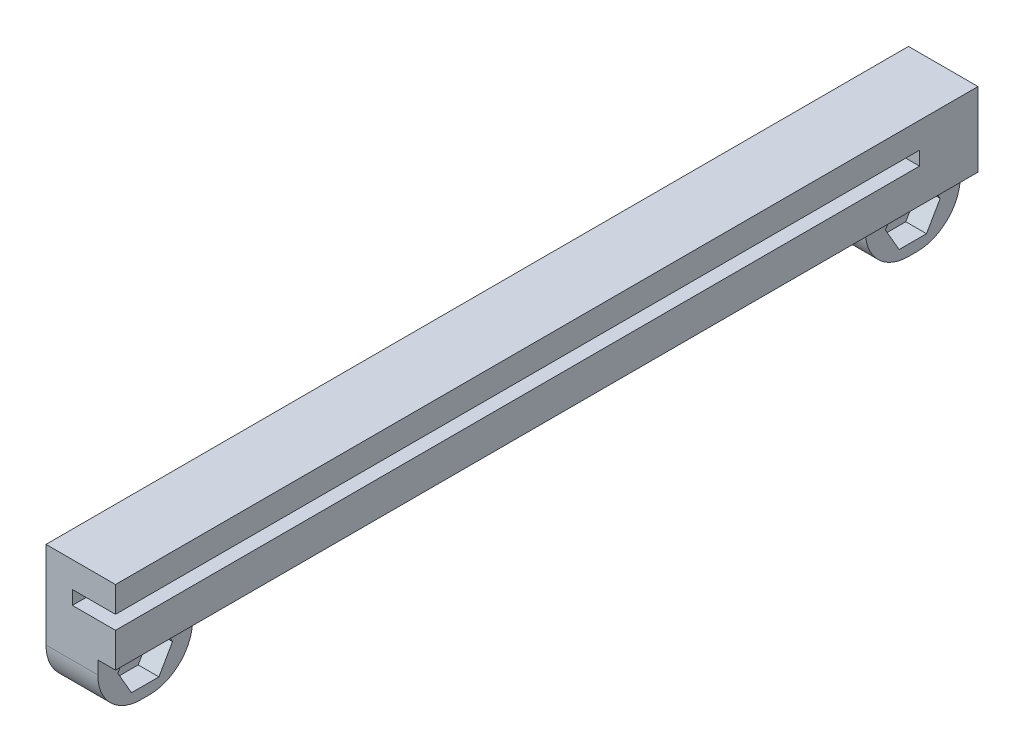
SolidWorks part; units mm, degrees
ref_plane "Front Plane" through (0, 0, 0) normal (0, 0, 1) x (1, 0, 0)
ref_plane "Top Plane" through (0, 0, 0) normal (0, 1, 0) x (1, 0, 0)
ref_plane "Right Plane" through (0, 0, 0) normal (1, 0, 0) x (0, 0, -1)
sketch "Sketch1" plane through (0, 0, 0) normal (0, 1, 0) x (1, 0, 0)
  line L1 (-3.5288, -50) -> (3.5288, -50)
  line L2 (-3.5288, -50) -> (-3.5288, 50)
  line L3 (-3.5288, 50) -> (3.5288, 50)
  line L4 (3.5288, -50) -> (3.5288, 50)
  line L5 (-3.5288, -50) -> (3.5288, 50) construction
  line L6 (-3.5288, 50) -> (3.5288, -50) construction
  point P0 (0, 0)
  dimension "D1" = 100
  dimension "D2" = 7.0575
extrude "Boss-Extrude2" add sketch "Sketch1" along normal blind 7.6
sketch "Sketch4" plane through (0, 7.6, 0) normal (0, 1, 0) x (1, 0, 0)
  line L0 (3.5288, -50) -> (3.5288, 50) construction
  line L1 (3.5288, 43.218) -> (-1.4713, 43.218)
  line L2 (3.5288, 43.218) -> (3.5288, -50)
  line L3 (3.5288, -50) -> (-1.4713, -50)
  line L4 (-1.4713, 43.218) -> (-1.4713, -50)
  line L6 (3.5288, 50) -> (-3.5288, 50) construction
  line L7 (-3.5288, 50) -> (-3.5288, -50) construction
  dimension "D1" = 6.782
  dimension "D2" = 2.0575
extrude "Cut-Extrude1" cut sketch "Sketch4" against normal blind 4.6
sketch "Sketch6" plane through (0, 7.6, 0) normal (0, 1, 0) x (1, 0, 0)
  line L1 (3.5288, 43.218) -> (-1.4713, 43.218)
  line L2 (3.5288, 43.218) -> (3.5288, -50)
  line L3 (3.5288, -50) -> (-1.4713, -50)
  line L4 (-1.4713, 43.218) -> (-1.4713, -50)
extrude "Boss-Extrude3" add sketch "Sketch6" against normal blind 3
sketch "Sketch8" plane through (0, 0, 0) normal (0, -1, 0) x (1, 0, 0)
  line L1 (-3.5288, 50) -> (3.5288, 50)
  line L2 (-3.5288, 50) -> (-3.5288, -50)
  line L3 (-3.5288, -50) -> (3.5288, -50)
  line L4 (3.5288, 50) -> (3.5288, -50)
extrude "Boss-Extrude4" add sketch "Sketch8" along normal blind 1
sketch "Sketch9" plane through (0, -1, 0) normal (0, -1, 0) x (1, 0, 0)
  line L1 (-3.5288, 50) -> (1.4712, 50)
  line L2 (-3.5288, 50) -> (-3.5288, 39)
  line L3 (-3.5288, 39) -> (1.4712, 39)
  line L4 (1.4712, 50) -> (1.4712, 39)
  line L5 (-3.5288, -50) -> (1.4712, -50)
  line L6 (-3.5288, -50) -> (-3.5288, -39)
  line L7 (-3.5288, -39) -> (1.4712, -39)
  line L8 (1.4712, -50) -> (1.4712, -39)
  point P10 (1.4712, -44.5)
  dimension "D1" = 11
  dimension "D2" = 11
  dimension "D3" = 5
  dimension "D4" = 5
extrude "Boss-Extrude5" add sketch "Sketch9" along normal blind 6.5 contours L2 L1 L4 L3 | L6 L5 L8 L7
sketch "Sketch10" plane through (1.4713, 0, 0) normal (1, 0, 0) x (0, 0, -1)
  line L0 (-50, -7.5) -> (-50, -1) construction
  line L1 (-46.0877, -0.75) -> (-47.6754, -3.5)
  line L2 (-47.6754, -3.5) -> (-46.0877, -6.25)
  line L3 (-46.0877, -6.25) -> (-42.9123, -6.25)
  line L4 (-42.9123, -6.25) -> (-41.3246, -3.5)
  line L5 (-41.3246, -3.5) -> (-42.9123, -0.75)
  line L6 (-42.9123, -0.75) -> (-46.0877, -0.75)
  line L7 (-50, -7.5) -> (-39, -7.5) construction
  line L8 (39, -7.5) -> (39, -1) construction
  line L9 (47.6754, -3.5) -> (46.0877, -0.75)
  line L10 (46.0877, -0.75) -> (42.9123, -0.75)
  line L11 (42.9123, -0.75) -> (41.3246, -3.5)
  line L12 (41.3246, -3.5) -> (42.9123, -6.25)
  line L13 (42.9123, -6.25) -> (46.0877, -6.25)
  line L14 (46.0877, -6.25) -> (47.6754, -3.5)
  line L15 (50, -7.5) -> (39, -7.5) construction
  circle A0 centre (-44.5, -3.5) radius 2.75 construction
  circle A1 centre (44.5, -3.5) radius 2.75 construction
  dimension "D1" = 5.5
  dimension "D2" = 5.5
  dimension "D3" = 1.25
  dimension "D4" = 5.5
  dimension "D5" = 1.25
  dimension "D6" = 5.5
extrude "Cut-Extrude2" cut sketch "Sketch10" against normal blind 2.4
sketch "Sketch11" plane through (-0.9287, 0, 0) normal (1, 0, 0) x (0, 0, -1)
  line L2 (-50, -7.5) -> (-39, -7.5) construction
  line L3 (-50, -7.5) -> (-50, -1) construction
  line L4 (39, -7.5) -> (39, -1) construction
  line L5 (50, -7.5) -> (39, -7.5) construction
  circle A0 centre (-44.5, -3.5) radius 1.5
  circle A1 centre (44.5, -3.5) radius 1.5
  dimension "D3" = 3
  dimension "D4" = 3
  dimension "D1" = 4
  dimension "D2" = 5.5
  dimension "D5" = 5.5
  dimension "D6" = 4
extrude "Cut-Extrude3" cut sketch "Sketch11" against normal through all contours A0 | A1
fillet "Fillet2" radius 5 4 edges at (-1.0288, -7.5, -50) (-1.0288, -7.5, -39) (-1.0288, -7.5, 39) (-1.0288, -7.5, 50)
sketch "Sketch13" plane through (-3.5288, 0, 0) normal (-1, 0, 0) x (0, 0, 1)
  line L0 (-45, -7.5) -> (-44, -7.5) construction
  line L1 (-39, -2.5) -> (-39, -1) construction
  line L2 (39, -1) -> (-39, -1) construction
  line L3 (39, -2.5) -> (39, -1) construction
  line L4 (45, -7.5) -> (44, -7.5) construction
  line L5 (50, 7.6) -> (50, -2.5) construction
  line L6 (-50, 7.6) -> (50, 7.6) construction
  line L7 (-50, 7.6) -> (-50, -2.5) construction
  line L8 (-45, -7.5) -> (-44, -7.5)
  line L9 (-39, -2.5) -> (-39, -1)
  line L10 (39, -1) -> (-39, -1)
  line L11 (39, -2.5) -> (39, -1)
  line L12 (45, -7.5) -> (44, -7.5)
  line L13 (50, 7.6) -> (50, -2.5)
  line L14 (-50, 7.6) -> (50, 7.6)
  line L15 (-50, 7.6) -> (-50, -2.5)
  circle A0 centre (-44.5, -3.5) radius 1.5 construction
  arc A1 (-50, -2.5) -> (-45, -7.5) centre (-45, -2.5) ccw construction
  arc A2 (-44, -7.5) -> (-39, -2.5) centre (-44, -2.5) ccw construction
  arc A3 (39, -2.5) -> (44, -7.5) centre (44, -2.5) ccw construction
  circle A4 centre (44.5, -3.5) radius 1.5 construction
  arc A5 (45, -7.5) -> (50, -2.5) centre (45, -2.5) ccw construction
  circle A6 centre (-44.5, -3.5) radius 1.5
  arc A7 (-50, -2.5) -> (-45, -7.5) centre (-45, -2.5) ccw
  arc A8 (-44, -7.5) -> (-39, -2.5) centre (-44, -2.5) ccw
  arc A9 (39, -2.5) -> (44, -7.5) centre (44, -2.5) ccw
  circle A10 centre (44.5, -3.5) radius 1.5
  arc A11 (45, -7.5) -> (50, -2.5) centre (45, -2.5) ccw
extrude "Boss-Extrude6" add sketch "Sketch13" along normal blind 1
